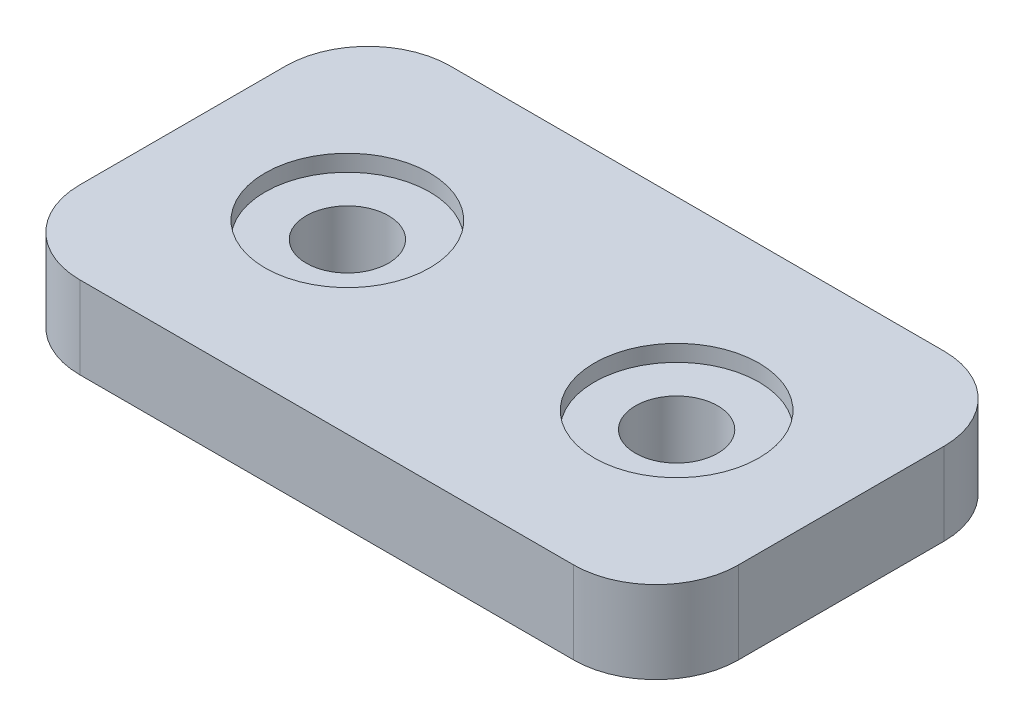
SolidWorks part; units mm, degrees
ref_plane "Front Plane" through (0, 0, 0) normal (0, 0, 1) x (1, 0, 0)
ref_plane "Top Plane" through (0, 0, 0) normal (0, 1, 0) x (1, 0, 0)
ref_plane "Right Plane" through (0, 0, 0) normal (1, 0, 0) x (0, 0, -1)
sketch "Sketch1" plane through (0, 0, 0) normal (0, 1, 0) x (1, 0, 0)
  line L1 (-50.8, -28.575) -> (50.8, -28.575)
  line L2 (-50.8, -28.575) -> (-50.8, 28.575)
  line L3 (-50.8, 28.575) -> (50.8, 28.575)
  line L4 (50.8, -28.575) -> (50.8, 28.575)
  line L5 (-50.8, -28.575) -> (50.8, 28.575) construction
  line L6 (-50.8, 28.575) -> (50.8, -28.575) construction
  point P0 (0, 0)
  dimension "D1" = 101.6
  dimension "D2" = 57.15
extrude "Boss-Extrude1" add sketch "Sketch1" along normal blind 12.7 contours L2 L3 L4 L1
sketch "Sketch2" plane through (0, 12.7, 0) normal (0, 1, 0) x (1, 0, 0)
  line L0 (-50.8, -28.575) -> (-50.8, 28.575) construction
  line L1 (-50.8, 28.575) -> (50.8, 28.575) construction
  line L2 (0, -6.985) -> (0, 6.985) construction
  circle A0 centre (-25.4, 0) radius 12.7
  circle A1 centre (25.4, 0) radius 12.7
  circle A2 centre (-25.4, 0) radius 6.35
  circle A3 centre (25.4, 0) radius 6.35
  dimension "D1" = 25.4
  dimension "D4" = 12.7
  dimension "D5" = 12.7
  dimension "D2" = 25.4
  dimension "D3" = 28.575
extrude "Cut-Extrude1" cut sketch "Sketch2" against normal blind 12.7 contours A2 | A3 region at (-25.4, 12.7, 0) region at (25.4, 12.7, 0)
extrude "Cut-Extrude2" cut sketch "Sketch2<3>" against normal blind 2.54 contours A0 A2 | A1 A3 region at (-37.7408, 12.7, 0) region at (13.0592, 12.7, 0)
sketch "Sketch2<3>" plane through (0, 12.7, 0) normal (0, 1, 0) x (1, 0, 0) same geometry as "Sketch2"
fillet "Fillet1" radius 12.7 4 edges at (50.8, 6.35, -28.575) (-50.8, 6.35, -28.575) (50.8, 6.35, 28.575) (-50.8, 6.35, 28.575)
